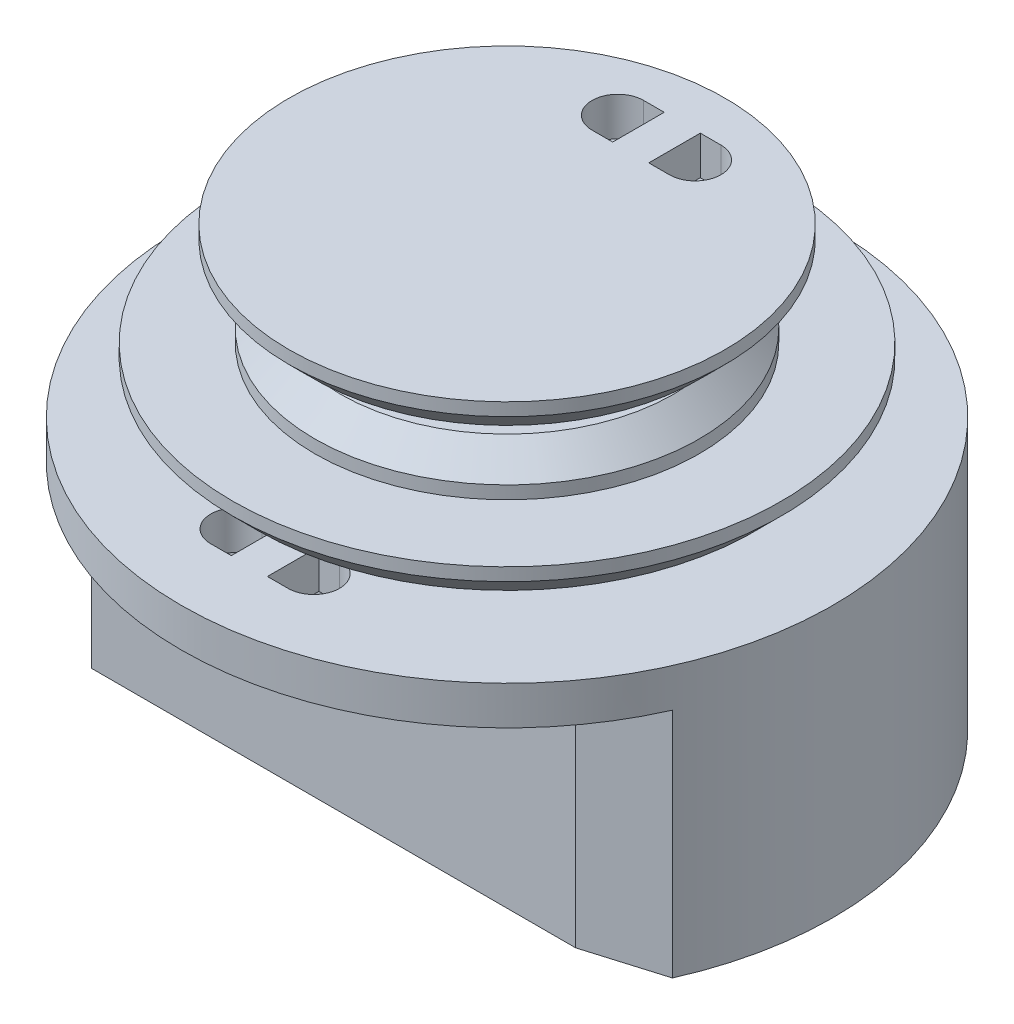
SolidWorks part; units mm, degrees
ref_plane "Front Plane" through (0, 0, 0) normal (0, 0, 1) x (1, 0, 0)
ref_plane "Top Plane" through (0, 0, 0) normal (0, 1, 0) x (1, 0, 0)
ref_plane "Right Plane" through (0, 0, 0) normal (1, 0, 0) x (0, 0, -1)
sketch "24" plane through (0, 0, 0) normal (0, 1, 0) x (1, 0, 0)
  circle A0 centre (0, 0) radius 7.6433
  dimension "D1" = 15.2866
extrude "Boss-Extrude1" add sketch "24" along normal blind 4
sketch "Sketch3" plane through (0, 0, 0) normal (0, 0, 1) x (1, 0, 0)
  line L0 (-7.6433, 4) -> (-10.6433, 4)
  line L1 (-10.6433, 4) -> (-10.6433, 2.5)
  line L5 (-12.6433, 1.5) -> (-12.6433, 0)
  line L6 (-7.6433, 4) -> (-7.6433, 0)
  line L7 (-12.6433, 0) -> (-7.6433, 0)
  line L8 (-10.6433, 2.5) -> (-7.6433, 2.5)
  line L9 (-7.6433, 2.5) -> (-7.6433, 1.5)
  line L10 (-7.6433, 1.5) -> (-12.6433, 1.5)
  dimension "D1" = 3
  dimension "D2" = 1.5
  dimension "D4" = 5
sketch "Sketch4" plane through (0, 0, 0) normal (1, 0, 0) x (0, 0, -1)
  line L0 (0, 4) -> (0, 0) construction
  line L1 (7.6433, 4) -> (-7.6433, 4) construction
revolve "Revolve1" add sketch "Sketch3" angle 360 about L0 region at (-9.1433, 3.25, 0) region at (-10.1433, 0.75, 0)
sketch "Sketch5" plane through (0, 4, 0) normal (0, 1, 0) x (1, 0, 0)
  circle A0 centre (0, 0) radius 4.4586
  dimension "D1" = 8.9172
extrude "Boss-Extrude2" add sketch "Sketch5" along normal blind 4
sketch "Sketch6" plane through (0, 0, 0) normal (0, 0, 1) x (1, 0, 0)
  line L0 (-4.4586, 8) -> (-8.4586, 8)
  line L1 (-8.4586, 8) -> (-8.4586, 6.5)
  line L3 (-8.4586, 6.5) -> (-4.4586, 6.5)
  line L6 (10.6433, 4) -> (-10.6433, 4) construction
  line L7 (-7.4586, 4) -> (-4.4586, 4)
  line L9 (-4.4586, 8) -> (-4.4586, 4)
  line L12 (-7.4586, 5.5) -> (-7.4586, 4)
  line L13 (-4.4586, 6.5) -> (-4.4586, 5.5)
  line L14 (-4.4586, 5.5) -> (-7.4586, 5.5)
  dimension "D1" = 4
  dimension "D2" = 1.5
  dimension "D3" = 3
revolve "Revolve2" add sketch "Sketch6" angle 360 about L0 region at (-6.4586, 7.25, 0) region at (-5.9586, 4.75, 0)
sketch "Sketch8" plane through (0, 0, 0) normal (0, -1, 0) x (1, 0, 0)
  line L0 (-1.5, 9) -> (1.5, 9) construction
  line L1 (-1.5, 10) -> (1.5, 10)
  line L2 (-1.5, 8) -> (1.5, 8)
  line L3 (0, 9) -> (0, 0) construction
  line L4 (0, 10) -> (0, 8) construction
  line L5 (-0.7, 10) -> (-0.7, 8)
  line L6 (0.7, 10) -> (0.7, 8)
  arc A0 (-1.5, 10) -> (-1.5, 8) centre (-1.5, 9) ccw
  arc A1 (1.5, 8) -> (1.5, 10) centre (1.5, 9) ccw
  circle A2 centre (0, 0) radius 12.6433 construction
  point P2 (0, 9)
  point P7 (2.5, 9)
  point P8 (-2.5, 9)
  dimension "D1" = 2
  dimension "D2" = 5
  dimension "D3" = 9
  dimension "D4" = 0.7
  dimension "D5" = 0.7
extrude "Cut-Extrude2" cut sketch "Sketch8" against normal blind 2 contours L1 A0 L2 L5 | L2 A1 L1 L6 region at (-1.5084, 0, 9) region at (1.5084, 0, 9)
sketch "Sketch9" plane through (0, 8, -8) normal (0, -1, 0) x (-1, 0, 0)
  line L0 (-1.5, -2.2) -> (1.5, -2.2) construction
  line L1 (-1.5, -1.2) -> (1.5, -1.2)
  line L2 (-1.5, -3.2) -> (1.5, -3.2)
  line L3 (0, -2.2) -> (0, -8) construction
  line L4 (0, -1.2) -> (0, -3.2) construction
  line L5 (-0.7, -1.2) -> (-0.7, -3.2)
  line L6 (0.7, -1.2) -> (0.7, -3.2)
  arc A0 (-1.5, -1.2) -> (-1.5, -3.2) centre (-1.5, -2.2) ccw
  arc A1 (1.5, -3.2) -> (1.5, -1.2) centre (1.5, -2.2) ccw
  point P2 (0, -2.2)
  point P7 (2.5, -2.2)
  point P8 (-2.5, -2.2)
  dimension "D1" = 2
  dimension "D2" = 5
  dimension "D3" = 5.8
  dimension "D4" = 0.7
  dimension "D5" = 0.7
extrude "Cut-Extrude3" cut sketch "Sketch9" along normal blind 2 contours A0 L1 L5 L2 | A1 L2 L6 L1 region at (1.5084, 8, -5.8) region at (-1.5084, 8, -5.8)
sketch "Sketch10" plane through (0, 0, 0) normal (0, -1, 0) x (1, 0, 0)
  line L0 (-11.1289, 6) -> (11.1289, 6)
  line L2 (-10.6433, 0) -> (10.6433, 0) construction
  line L3 (-7.25, 0) -> (0, 0) construction
  arc A1 (10.4428, -7.1275) -> (11.1289, 6) centre (0, 0) ccw
  circle A2 centre (-7.25, 0) radius 0.75
  circle A3 centre (7.25, 0) radius 0.75
  circle A4 centre (0, 0) radius 12.6433 construction
  arc A5 (-11.1289, 6) -> (11.1289, 6) centre (0, 0) ccw
  circle M5 centre (0, 0) radius 12.6433
  dimension "D4" = 1.5
  dimension "D2" = 6
  dimension "D5" = 7.25
  dimension "D6" = 7.25
extrude "Boss-Extrude4" add sketch "Sketch10" along normal blind 9 contours L0 A3 A2 M5 region at (0, 0, -2.3359)
chamfer "Chamfer1" distance 1 angle 45 5 edges at (0, 2.5, 10.6433) (0, 5.5, 7.4586) (0, 6.5, 8.4586) (11.1289, -4.5, 6) (-11.1289, -4.5, 6) first distance on face at (0, 2.5, 7.6433) first distance on face at (0, 4, 7.4586) first distance on face at (0, 6.5, 4.4586) first distance on face at (0, -4.5, 3) first distance on face at (0, -4.5, 6)
